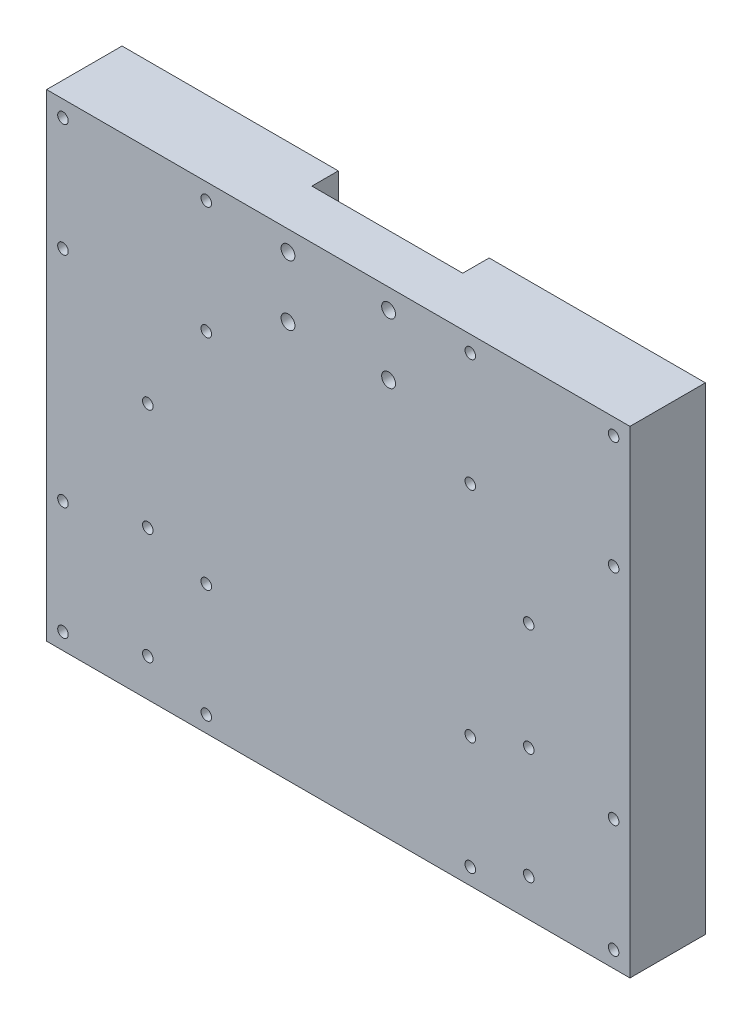
SolidWorks part; units mm, degrees
ref_plane "Piano frontale" through (0, 0, 0) normal (0, 0, 1) x (1, 0, 0)
ref_plane "Piano superiore" through (0, 0, 0) normal (0, 1, 0) x (1, 0, 0)
ref_plane "Piano destro" through (0, 0, 0) normal (1, 0, 0) x (0, 0, -1)
sketch "Schizzo1" plane through (0, 0, 0) normal (0, 0, 1) x (1, 0, 0)
  line L1 (116, -95) -> (-116, -95)
  line L2 (116, -95) -> (116, 95)
  line L3 (116, 95) -> (-116, 95)
  line L4 (-116, -95) -> (-116, 95)
  line L5 (116, -95) -> (-116, 95) construction
  line L6 (116, 95) -> (-116, -95) construction
  point P0 (0, 0)
  dimension "D1" = 232
  dimension "D2" = 190
extrude "Estrusione-Estrusione1" add sketch "Schizzo1" along normal blind 30
sketch "Schizzo3" plane through (0, 0, 30) normal (0, 0, 1) x (1, 0, 0)
  line L0 (20, 7) -> (-20, 7) construction
  line L1 (-20, 7) -> (20, -17) construction
  line L2 (20, -17) -> (20, 7) construction
  line L3 (20, 7) -> (-20, -17) construction
  line L4 (-20, -17) -> (-20, 7) construction
  line L5 (-20, -17) -> (20, -17) construction
  circle A8 centre (20, 7) radius 3
  circle A9 centre (-20, 7) radius 3
  circle A10 centre (-20, -17) radius 3
  circle A11 centre (20, -17) radius 3
  point P21 (0, -5)
  dimension "D1" = 40
  dimension "D2" = 24
sketch "Schizzo4" plane through (0, 95, 0) normal (0, 1, 0) x (1, 0, 0)
  line L0 (116, 0) -> (-116, 0) construction
  line L1 (30, 0) -> (-30, 0)
  line L2 (30, 0) -> (30, -10.5)
  line L3 (30, -10.5) -> (-30, -10.5)
  line L4 (-30, 0) -> (-30, -10.5)
  dimension "D1" = 10.5
extrude "Taglio-Estrusione2" cut sketch "Schizzo4" against normal through all
sketch "Sketch1" plane through (0, 0, 0) normal (0, 0, -1) x (-1, 0, 0)
  point P0 (-109.5, 88.5)
  point P1 (-109.5, 43.5)
  point P3 (-52.5, 88.5)
  point P5 (-52.5, 43.5)
  point P7 (-52.5, -43.5)
  point P9 (-109.5, -43.5)
  point P11 (-109.5, -88.5)
  point P13 (-52.5, -88.5)
  point P15 (52.5, -88.5)
  point P17 (109.5, -88.5)
  point P19 (109.5, -43.5)
  point P21 (52.5, -43.5)
  point P23 (52.5, 43.5)
  point P25 (109.5, 43.5)
  point P27 (109.5, 88.5)
  point P29 (52.5, 88.5)
hole_wizard "Tap Drill for M5 Tap1" positions "Sketch2" profile "Sketch3" hole size "M5" standard "ISO" end condition through all
sketch "Sketch2" plane through (0, 0, 0) normal (0, 0, -1) x (-1, 0, 0)
  point P0 (-109.5, 88.5)
  point P3 (-109.5, 43.5)
  point P6 (-52.5, 43.5)
  point P9 (-52.5, 88.5)
  point P12 (52.5, 88.5)
  point P15 (109.5, 88.5)
  point P18 (109.5, 43.5)
  point P21 (52.5, 43.5)
  point P24 (52.5, -43.5)
  point P27 (109.5, -43.5)
  point P30 (109.5, -88.5)
  point P33 (52.5, -88.5)
  point P36 (-52.5, -88.5)
  point P39 (-52.5, -43.5)
  point P42 (-109.5, -43.5)
  point P45 (-109.5, -88.5)
sketch "Sketch3" plane through (109.5, 88.5, 0) normal (1, 0, 0) x (0, 1, 0)
  line L0 (0, 0) -> (0, 30)
  line L1 (0, 30) -> (2.1, 30)
  line L2 (2.1, 30) -> (2.1, 0)
  line L5 (2.1, 0) -> (0, 0)
  line L11 (0, -6.35) -> (0, 107.95) construction
  dimension "Thru Hole Dia." = 4.2
  dimension "Thru Hole Depth" = 30
hole_wizard "M5 Clearance Hole1" positions "Sketch4" profile "Sketch5" hole size "M5" standard "ISO" end condition through all
sketch "Sketch4" plane through (0, 0, 30) normal (0, 0, 1) x (1, 0, 0)
  point P0 (-20, 87)
  point P3 (20, 87)
  point P6 (20, 63)
  point P9 (-20, 63)
sketch "Sketch5" plane through (-20, 87, 30) normal (1, 0, 0) x (0, -1, 0)
  line L0 (0, 0) -> (0, 30)
  line L1 (0, 30) -> (2.75, 30)
  line L2 (2.75, 30) -> (2.75, 0)
  line L5 (2.75, 0) -> (0, 0)
  line L11 (0, -6.35) -> (0, 107.95) construction
  dimension "Thru Hole Dia." = 5.5
  dimension "Thru Hole Depth" = 30
hole_wizard "Tap Drill for M5 Tap3" positions "Sketch6" profile "Sketch7" hole size "M5" standard "ISO" end condition up to next
sketch "Sketch6" plane through (0, 0, 30) normal (0, 0, 1) x (1, 0, 0)
  point P0 (-75.75, 7)
  point P6 (-75.75, -80)
  point P8 (75.75, 7)
  point P14 (75.75, -80)
  point P23 (-75.75, -35.7925)
  point P25 (75.75, -35.7925)
sketch "Sketch7" plane through (-75.75, 7, 30) normal (1, 0, 0) x (0, -1, 0)
  line L0 (0, 0) -> (0, 30)
  line L1 (0, 30) -> (2.1, 30)
  line L2 (2.1, 30) -> (2.1, 0)
  line L5 (2.1, 0) -> (0, 0)
  line L11 (0, -6.35) -> (0, 107.95) construction
  dimension "Thru Hole Dia." = 4.2
  dimension "Thru Hole Depth" = 30
